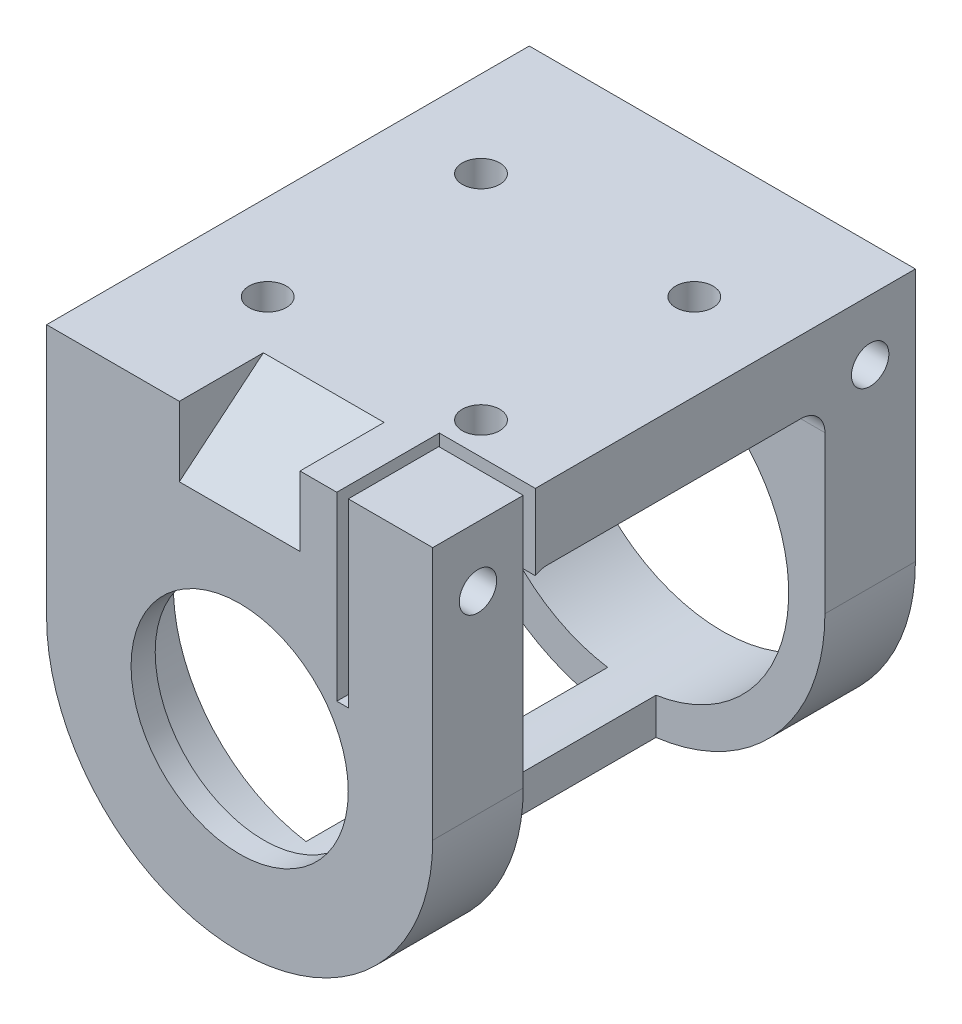
SolidWorks part; units mm, degrees
material "PLA"
ref_plane "Front Plane" through (0, 0, 0) normal (0, 0, 1) x (1, 0, 0)
ref_plane "Top Plane" through (0, 0, 0) normal (0, 1, 0) x (1, 0, 0)
ref_plane "Right Plane" through (0, 0, 0) normal (1, 0, 0) x (0, 0, -1)
sketch "Sketch1" plane through (0, 0, 0) normal (0, 0, 1) x (1, 0, 0)
  line L0 (-16, 0) -> (-16, 16)
  line L1 (-16, 16) -> (16, 16)
  line L2 (16, 16) -> (16, 0)
  circle A0 centre (0, 0) radius 13
  circle A1 centre (0, 0) radius 16
  point P12 (0, 0)
  dimension "D1" = 26
  dimension "D2" = 32
extrude "Boss-Extrude1" add sketch "Sketch1" along normal mid plane 40 contours A1 L1 L0 | A1 L2 L1 | A1 A0 region at (-10.9937, 10.9937, 0) region at (-12.4261, 12.4261, 0) region at (12.4261, 12.4261, 0)
sketch "Sketch4" plane through (0, 16, 0) normal (0, 1, 0) x (1, 0, 0)
  line L0 (-16, -20) -> (-16, 20) construction
  line L1 (-16, 20) -> (16, 20)
  line L2 (-16, 20) -> (-16, -20)
  line L3 (-16, -20) -> (16, -20)
  line L4 (16, 20) -> (16, -20)
  line L5 (16, -20) -> (16, 20) construction
  line L6 (-44.2539, 0) -> (44.2539, 0) construction
  line M5 (16, 20) -> (-16, 20)
  line M6 (-16, 20) -> (-16, -20)
  line M7 (-16, -20) -> (16, -20)
  line M8 (16, -20) -> (16, 20)
  dimension "D1" = 40
  dimension "D2" = 20
extrude "Boss-Extrude3" add sketch "Sketch4" along normal blind 5 contours M8 M5 M6 M7 region at (0, 16, 0)
sketch "Sketch5" plane through (16, 0, 0) normal (1, 0, 0) x (0, 0, -1)
  line L1 (-12.5, 15) -> (12.5, 15)
  line L2 (-12.5, 15) -> (-12.5, -16)
  line L3 (-12.5, -16) -> (12.5, -16)
  line L4 (12.5, 15) -> (12.5, -16)
  line L5 (0, 44.2539) -> (0, -44.2539) construction
  line L6 (-20, 21) -> (20, 21) construction
  line L8 (55, 0) -> (-55, 0) construction
  point P4 (12.5, -15.5543)
  dimension "D1" = 25
  dimension "D2" = 12.5
  dimension "D3" = 6
  dimension "D4" = 16
extrude "Cut-Extrude2" cut sketch "Sketch5" along direction (-1, 0, 0) on the side against the normal offset from surface (14 mm away) 2 up to plane "Right Plane"
sketch "Sketch6" plane through (0, 21, 0) normal (0, 1, 0) x (1, 0, 0)
  line L0 (-44.2539, 0) -> (44.2539, 0) construction
  line L1 (-8.8388, 8.8388) -> (8.8388, 8.8388) construction
  line L2 (-8.8388, 8.8388) -> (-8.8388, -8.8388) construction
  line L3 (-8.8388, -8.8388) -> (8.8388, -8.8388) construction
  line L4 (8.8388, 8.8388) -> (8.8388, -8.8388) construction
  line L5 (0, -44.7868) -> (0, 44.7868) construction
  circle A0 centre (-8.8388, 8.8388) radius 1.55
  circle A1 centre (8.8388, 8.8388) radius 1.55
  circle A2 centre (8.8388, -8.8388) radius 1.55
  circle A3 centre (-8.8388, -8.8388) radius 1.55
  point P6 (-8.8388, 0)
  point P7 (0, 8.8388)
  dimension "D1" = 25
  dimension "D2" = 3.1
extrude "MotorMountHoles" cut sketch "Sketch6" against normal blind 6
sketch "Sketch9" plane through (0, 0, 20) normal (0, 0, 1) x (1, 0, 0)
  circle A0 centre (0, 0) radius 13
  circle A1 centre (0, 0) radius 9
  circle M13 centre (0, 0) radius 13
  dimension "D1" = 18
  dimension "D2" = 26
extrude "EndStopper" add sketch "Sketch9" against normal blind 2 contours A1 M13 region at (-12.6323, 0, 20)
sketch "Sketch10" plane through (0, 0, 0) normal (1, 0, 0) x (0, 0, -1)
  line L0 (55, 0) -> (-55, 0) construction
  line L1 (-12.5, 15) -> (12.5, 15)
  line L2 (-12.5, 15) -> (-12.5, -16)
  line L3 (-12.5, -16) -> (12.5, -16)
  line L4 (12.5, 15) -> (12.5, -16)
  dimension "D1" = 16
extrude "Cut-Extrude7" cut sketch "Sketch10" along normal offset from surface (14 mm away) 2 from surface up to plane "Right Plane" starting at face at (-16, 10.5, 0)
sketch "Sketch12" plane through (0, 0, 0) normal (1, 0, 0) x (0, 0, -1)
  line L0 (-30.459, 12.329) -> (0, 37.5809) construction
  line L1 (0, 44.2539) -> (0, -44.2539) construction
  line L2 (-10.1062, 43.5673) -> (4.9914, 25.3565) construction
  line L3 (0, 37.5809) -> (-30.459, 12.329)
ref_plane "Plane1" through (0, 12.7812, -15.4168) normal (0, 0.6382, -0.7698) x (-1, 0, 0)
sketch "Sketch13" plane through (0, 12.7812, -15.4168) normal (0, 0.6382, -0.7698) x (-1, 0, 0)
  line L0 (0, 44.7868) -> (0, -44.7868) construction
  line L1 (-5, 34.4844) -> (5, 34.4844)
  line L2 (-5, 34.4844) -> (-5, 24.4844)
  line L3 (-5, 24.4844) -> (5, 24.4844)
  line L4 (5, 34.4844) -> (5, 24.4844)
  dimension "D1" = 10
  dimension "D2" = 10
  dimension "D3" = 5
sweep "Cut-Sweep1" cut profiles "Sketch13" path "Sketch12"
fillet "Fillet2" radius 2 4 edges at (9, 15, 12.5) (-9, 15, 12.5) (-9, 15, -12.5) (9, 15, -12.5)
sketch "Sketch18" plane through (16, 0, 0) normal (1, 0, 0) x (0, 0, -1)
  line L0 (-20, 21) -> (20, 21) construction
  line L1 (-12.9591, 16) -> (-14.6046, 18.85)
  line L2 (-14.6046, 18.85) -> (-17.8954, 18.85)
  line L3 (-17.8954, 18.85) -> (-19.5409, 16)
  line L4 (-19.5409, 16) -> (-17.8954, 13.15)
  line L5 (-17.8954, 13.15) -> (-14.6046, 13.15)
  line L6 (-14.6046, 13.15) -> (-12.9591, 16)
  line L7 (19.5409, 16) -> (17.8954, 18.85)
  line L8 (17.8954, 18.85) -> (14.6046, 18.85)
  line L9 (14.6046, 18.85) -> (12.9591, 16)
  line L10 (12.9591, 16) -> (14.6046, 13.15)
  line L11 (14.6046, 13.15) -> (17.8954, 13.15)
  line L12 (17.8954, 13.15) -> (19.5409, 16)
  line L13 (20, 21) -> (20, 0) construction
  line L14 (-20, 21) -> (-20, 0) construction
  circle A0 centre (-16.25, 16) radius 2.85 construction
  circle A1 centre (16.25, 16) radius 2.85 construction
  dimension "D1" = 5.7
  dimension "D2" = 5
  dimension "D3" = 3.75
  dimension "D4" = 3.75
extrude "Cut-Extrude12" cut sketch "Sketch18" against normal blind 2.7 from offset 5.2 offset against normal yes
sketch "Sketch19" plane through (16, 0, 0) normal (1, 0, 0) x (0, 0, -1)
  line L0 (-20, 21) -> (20, 21) construction
  line L1 (20, 21) -> (20, 0) construction
  line L2 (-20, 21) -> (-20, 0) construction
  circle A0 centre (-16.25, 16) radius 1.55
  circle A1 centre (16.25, 16) radius 1.55
  point P8 (0, 0)
  dimension "D1" = 5
  dimension "D4" = 3.75
  dimension "D3" = 3.1
  dimension "D2" = 3.75
extrude "Cut-Extrude13" cut sketch "Sketch19" against normal blind 9
sketch "Sketch20" plane through (0, 21, 0) normal (0, 1, 0) x (1, 0, 0)
  line L0 (5, -20) -> (16, -20) construction
  line L1 (17, -21) -> (8.0491, -21)
  line L2 (17, -21) -> (17, -11.5)
  line L3 (17, -11.5) -> (8.0491, -11.5)
  line L4 (8.0491, -21) -> (8.0491, -11.5)
  line L5 (9, -12.5) -> (16, -12.5)
  line L6 (9, -12.5) -> (9, -20)
  line L7 (9, -20) -> (16, -20)
  line L8 (16, -12.5) -> (16, -20)
  line L9 (0, -44.7868) -> (0, 44.7868) construction
  point P8 (19.4152, -22.0832)
  point P9 (0, 0)
  point P11 (7.2772, -20)
  dimension "D1" = 7.5
  dimension "D2" = 9
  dimension "D3" = 9.5
  dimension "D4" = 8.0491
  dimension "D5" = 1
  dimension "D6" = 1
extrude "Cut-Extrude15" cut sketch "Sketch20" against normal blind 15
equation "\"InnerDiam\"=26"
equation "\"D1@Sketch1\"=\"InnerDiam\""
equation "\"OuterDiam\"=32"
equation "\"D2@Sketch1\"=\"OuterDiam\""
equation "\"TightenGap\"=1.5"
equation "\"ClampLen\"=10.5"
equation "\"Thick\"=40"
equation "\"D1@Boss-Extrude1\"=\"Thick\""
equation "\"MotBaseThick\"=5"
equation "\"D1@Boss-Extrude3\"=\"MotBaseThick\""
equation "\"TopPlateLen\"=35"
equation "\"D1@Sketch4\"=\"Thick\""
equation "\"D2@Sketch4\"=\"Thick\"/2"
equation "\"D1@Sketch5\"=\"Thick\"- 2 * \"ClampWidth\""
equation "\"D2@Sketch5\"=(\"Thick\"- 2 * \"ClampWidth\")/2"
equation "\"MotorMountDiam\"=25"
equation "\"D1@Sketch6\"=\"MotorMountDiam\""
equation "\"ClampWidth\"= 7.5"
equation "\"D2@Sketch9\"=\"InnerDiam\""
equation "\"D19@Cut-Extrude2\"=\"OuterDiam\"/2"
equation "\"D4@Sketch5\"=\"OuterDiam\"/2"
equation "\"D1@Sketch10\"=\"OuterDiam\"/2"
equation "\"NutSize\"=5.7"
equation "\"D1@Sketch18\"=\"NutSize\""
equation "\"NutHeight\"=2.7"
equation "\"D1@Cut-Extrude12\"=\"NutHeight\""
equation "\"D4@Sketch19\"=\"ClampWidth\"/2"
equation "\"D2@Sketch19\"=\"ClampWidth\"/2"
equation "\"D3@Sketch18\"=\"ClampWidth\"/2"
equation "\"D4@Sketch18\"=\"ClampWidth\"/2"
equation "\"D1@Sketch20\"=\"ClampWidth\""
equation "\"D3@Sketch20\"=\"ClampWidth\"+2"
